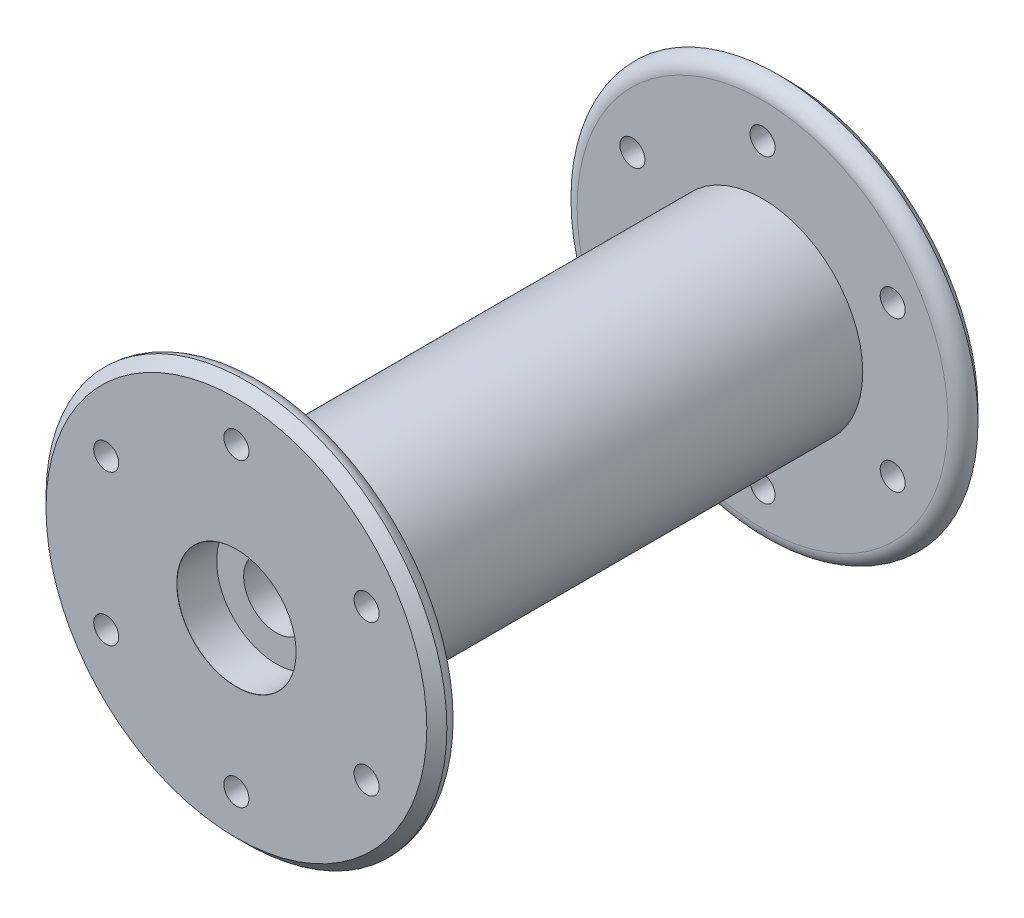
SolidWorks part; units mm, degrees
ref_plane "Front Plane" through (0, 0, 0) normal (0, 0, 1) x (1, 0, 0)
ref_plane "Top Plane" through (0, 0, 0) normal (0, 1, 0) x (1, 0, 0)
ref_plane "Right Plane" through (0, 0, 0) normal (1, 0, 0) x (0, 0, -1)
sketch "Sketch1" plane through (0, 0, 0) normal (0, 0, 1) x (1, 0, 0)
  circle A0 centre (0, 0) radius 20
  dimension "ShaftDiameter" = 40
extrude "Boss-Extrude1" add sketch "Sketch1" along normal mid plane 100
sketch "Sketch2" plane through (0, 0, 50) normal (0, 0, 1) x (1, 0, 0)
  circle A0 centre (0, 0) radius 40
  dimension "CapDiameter" = 80
extrude "Boss-Extrude2" add sketch "Sketch2" along normal blind 5
chamfer "Chamfer1" distance 2 angle 45 1 edges at (40, 0, 55)
sketch "Sketch3" plane through (0, 0, 55) normal (0, 0, 1) x (1, 0, 0)
  line L0 (0, 40) -> (0, 20) construction
  circle A0 centre (0, 0) radius 40 construction
  circle A1 centre (0, 0) radius 20 construction
  circle A2 centre (0, 30) radius 2.5
  dimension "D1" = 5
extrude "Cut-Extrude1" cut sketch "Sketch3" against normal through all
pattern_circular "CirPattern1" count 6 over 360 about axis through (0, 0, 55) along (0, 0, 1) of "Cut-Extrude1"
fillet "Fillet1" radius 3 1 edges at (40, 0, 50)
hole_wizard "CBORE for M12 Hex Head Bolt1" positions "Sketch4" profile "Sketch5" counterbore size "M12" standard "ANSI Metric" end condition through all
sketch "Sketch4" plane through (0, 0, 55) normal (0, 0, 1) x (1, 0, 0)
  point P0 (0, 0)
sketch "Sketch5" plane through (0, 0, 55) normal (1, 0, 0) x (0, -1, 0)
  line L0 (0, 0) -> (0, 110)
  line L1 (0, 110) -> (6.5, 110)
  line L3 (6.5, 110) -> (6.5, 7.95)
  line L4 (11.89, 7.95) -> (6.5, 7.95)
  line L5 (11.89, 7.95) -> (11.89, 0.025)
  line L6 (11.89, 0.025) -> (11.915, 0)
  line L7 (11.915, 0) -> (0, 0)
  line L8 (-11.89, 0.025) -> (-11.915, 0) construction
  line L11 (0, -6.35) -> (0, 107.95) construction
  dimension "Thru Hole Dia." = 13
  dimension "Thru Hole Depth" = 110
  dimension "C'Bore Dia." = 23.78
  dimension "C'Bore Depth" = 7.95
  dimension "Near C'Sink Dia." = 23.83
  dimension "Near C'Sink Angle" = 90
mirror "Mirror2" about plane through (0, 0, 0) normal (0, 0, 1) of "CirPattern1", "Fillet1", "CBORE for M12 Hex Head Bolt1", "Cut-Extrude1", "Chamfer1", "Boss-Extrude2"
